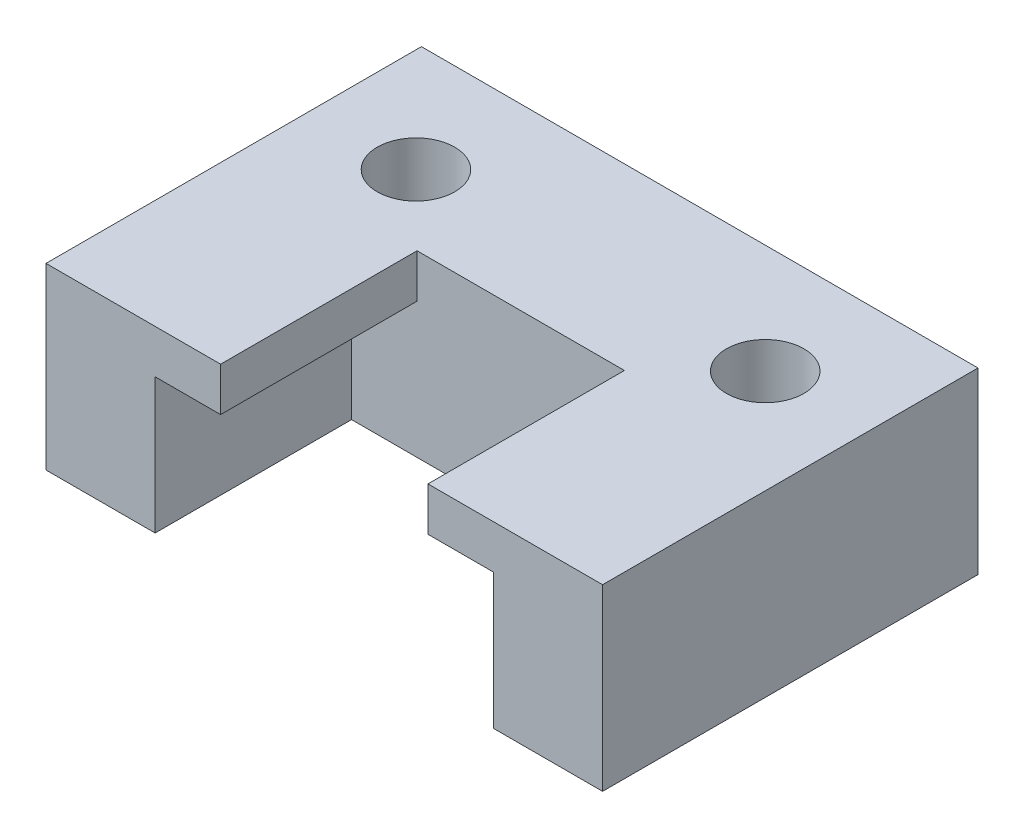
SolidWorks part; units mm, degrees
ref_plane "Front Plane" through (0, 0, 0) normal (0, 0, 1) x (1, 0, 0)
ref_plane "Top Plane" through (0, 0, 0) normal (0, 1, 0) x (1, 0, 0)
ref_plane "Right Plane" through (0, 0, 0) normal (1, 0, 0) x (0, 0, -1)
sketch "Sketch1" plane through (0, 0, 0) normal (0, 1, 0) x (1, 0, 0)
  line L0 (-8, 0) -> (8, 0) construction
  line L1 (-12.75, 5) -> (12.75, 5)
  line L2 (12.75, 5) -> (12.75, -12.2)
  line L3 (12.75, -12.2) -> (7.75, -12.2)
  line L4 (7.75, -12.2) -> (7.75, -3.2)
  line L5 (7.75, -3.2) -> (-7.75, -3.2)
  line L6 (-7.75, -3.2) -> (-7.75, -12.2)
  line L7 (-7.75, -12.2) -> (-12.75, -12.2)
  line L8 (-12.75, -12.2) -> (-12.75, 5)
  line L9 (-7.75, -12.2) -> (-4.75, -12.2)
  line L10 (-4.75, -12.2) -> (-4.75, -3.2)
  line L11 (4.75, -3.2) -> (4.75, -12.2)
  line L12 (4.75, -12.2) -> (7.75, -12.2)
  circle A0 centre (-8, 0) radius 1.775
  circle A1 centre (8, 0) radius 1.775
  point P4 (0, 0)
  point P14 (0, -3.2)
  dimension "D1" = 3.55
  dimension "D2" = 16
  dimension "D3" = 15.5
  dimension "D4" = 5
  dimension "D5" = 3.2
  dimension "D6" = 5
  dimension "D7" = 9
  dimension "D8" = 9.5
extrude "Boss-Extrude1" add sketch "Sketch1" along normal blind 6.2 contours L8 L7 L6 L5 L4 L3 L2 L1 A0 A1 region at (0, 0, 1.8074)
extrude "Boss-Extrude2" add sketch "Sketch1<3>" along normal blind 2 from surface contours L8 L7 L6 L5 L4 L3 L2 L1 A0 A1 | L9 L10 L5 L6 | L11 L12 L4 L5 region at (0, 0, 1.8074) region at (-6.25, 0, 7.7) region at (6.25, 0, 7.7) starting at face at (8, 6.2, 1.775)
sketch "Sketch1<3>" plane through (0, 0, 0) normal (0, 1, 0) x (1, 0, 0) same geometry as "Sketch1"
